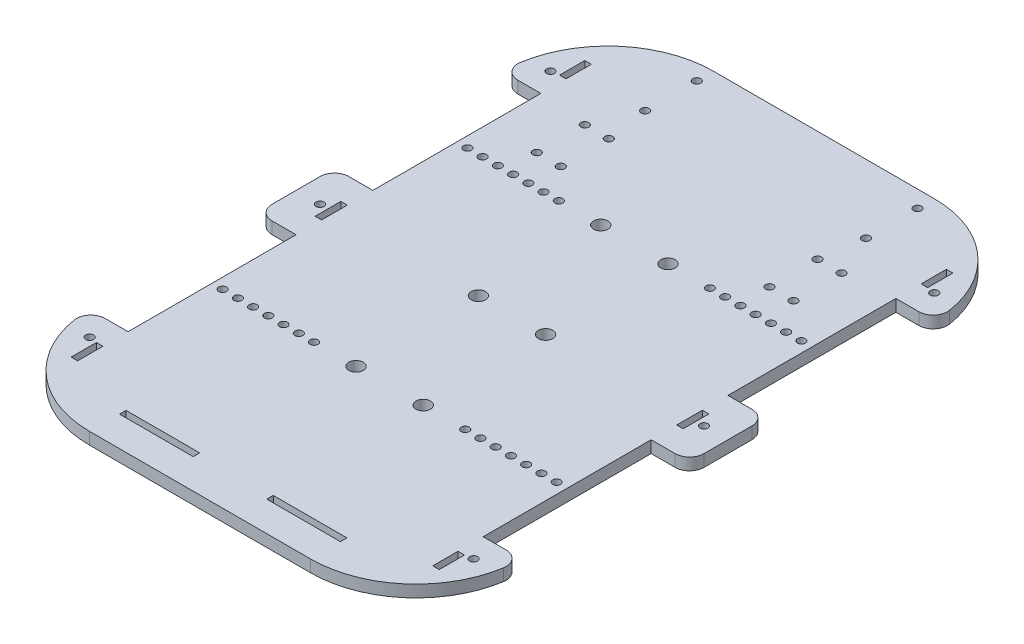
SolidWorks part; units mm, degrees
ref_plane "Ön Düzlem" through (0, 0, 0) normal (0, 0, 1) x (1, 0, 0)
ref_plane "Üst Düzlem" through (0, 0, 0) normal (0, 1, 0) x (1, 0, 0)
ref_plane "Sağ Düzlem" through (0, 0, 0) normal (1, 0, 0) x (0, 0, -1)
sketch "Sketch2" plane through (0, 0, 0) normal (0, 1, 0) x (1, 0, 0)
  line L0 (-74, -86) -> (-74, -51) construction
  line L1 (46, -130) -> (-46, -130)
  line L2 (90, -10) -> (90, 10)
  line L3 (46, 130) -> (-46, 130)
  line L4 (-90, -10) -> (-90, 10)
  line L5 (90, -130) -> (-90, 130) construction
  line L6 (90, 130) -> (-90, -130) construction
  line L7 (-83.5233, 86) -> (-74, 86)
  line L9 (-84, 16) -> (-74, 16)
  line L10 (-74, 86) -> (-74, 16)
  line L11 (-83.5233, -86) -> (-74, -86)
  line L13 (-84, -16) -> (-74, -16)
  line L14 (-74, -86) -> (-74, -16)
  line L15 (83.5233, 86) -> (74, 86)
  line L17 (84, 16) -> (74, 16)
  line L18 (74, 86) -> (74, 16)
  line L19 (83.5233, -86) -> (74, -86)
  line L21 (84, -16) -> (74, -16)
  line L22 (74, -86) -> (74, -16)
  line L23 (-74, 51) -> (74, 51) construction
  line L24 (-74, -51) -> (74, -51) construction
  line L26 (-74, 96.51) -> (-76.7, 96.51)
  line L27 (-76.7, 96.51) -> (-76.7, 107.02)
  line L28 (-74, 107.02) -> (-76.7, 107.02)
  line L29 (-74, 96.51) -> (-74, 107.02)
  line L30 (74, 96.51) -> (74, 107.02)
  line L31 (74, 107.02) -> (76.7, 107.02)
  line L32 (76.7, 96.51) -> (76.7, 107.02)
  line L33 (74, 96.51) -> (76.7, 96.51)
  line L34 (74, -107.02) -> (76.7, -107.02)
  line L35 (76.7, -96.51) -> (76.7, -107.02)
  line L36 (74, -96.51) -> (74, -107.02)
  line L37 (74, -96.51) -> (76.7, -96.51)
  line L38 (-74, -96.51) -> (-74, -107.02)
  line L39 (-74, -107.02) -> (-76.7, -107.02)
  line L40 (-76.7, -96.51) -> (-76.7, -107.02)
  line L41 (-74, -96.51) -> (-76.7, -96.51)
  line L42 (-74, 5.3333) -> (-74, -5.3333)
  line L43 (74, 5.3333) -> (74, -5.3333)
  line L44 (-74, 5.3333) -> (-76.7, 5.3333)
  line L45 (-76.7, 5.3333) -> (-76.7, -5.3333)
  line L46 (-76.7, -5.3333) -> (-74, -5.3333)
  line L47 (74, 5.3333) -> (76.7, 5.3333)
  line L48 (76.7, 5.3333) -> (76.7, -5.3333)
  line L49 (76.7, -5.3333) -> (74, -5.3333)
  line L52 (15.34, -117.53) -> (46.02, -117.53)
  line L54 (-15.34, -117.53) -> (-46.02, -117.53)
  line L56 (46.02, -117.53) -> (46.02, -114.83)
  line L57 (46.02, -114.83) -> (15.34, -114.83)
  line L59 (-15.34, -114.83) -> (-46.02, -114.83)
  line L60 (-46.02, -114.83) -> (-46.02, -117.53)
  line L62 (15.34, -117.53) -> (15.34, -114.83)
  line L63 (-15.34, -117.53) -> (-15.34, -114.83)
  arc A2 (-46, -130) -> (-89.4481, -92.9474) centre (-46, -86) cw
  arc A3 (-89.4481, 92.9474) -> (-46, 130) centre (-46, 86) cw
  arc A4 (89.4481, 92.9474) -> (46, 130) centre (46, 86) ccw
  arc A5 (89.4481, -92.9474) -> (46, -130) centre (46, -86) cw
  arc A6 (-84, 16) -> (-90, 10) centre (-84, 10) ccw
  arc A7 (-84, -16) -> (-90, -10) centre (-84, -10) cw
  arc A8 (90, 10) -> (84, 16) centre (84, 10) ccw
  arc A9 (90, -10) -> (84, -16) centre (84, -10) cw
  arc A10 (-89.4481, -92.9474) -> (-83.5233, -86) centre (-83.5233, -92) cw
  arc A11 (83.5233, -86) -> (89.4481, -92.9474) centre (83.5233, -92) cw
  arc A12 (-89.4481, 92.9474) -> (-83.5233, 86) centre (-83.5233, 92) ccw
  arc A13 (89.4481, 92.9474) -> (83.5233, 86) centre (83.5233, 92) cw
  point P0 (0, 0)
  point P34 (-90, -16)
  point P39 (90, -16)
  point P46 (-90, 86)
  point P49 (90, 86)
  dimension "D3" = 44
  dimension "D4" = 44
  dimension "D5" = 44
  dimension "D6" = 44
  dimension "D15" = 6
  dimension "D16" = 6
  dimension "D17" = 6
  dimension "D18" = 6
  dimension "D19" = 6
  dimension "D20" = 6
  dimension "D21" = 6
  dimension "D22" = 6
  dimension "D1" = 260
  dimension "D2" = 180
  dimension "D7" = 16
  dimension "D8" = 70
  dimension "D9" = 16
  dimension "D10" = 70
  dimension "D11" = 70
  dimension "D12" = 16
  dimension "D13" = 16
  dimension "D14" = 70
extrude "Boss-Extrude4" add sketch "Sketch2" along normal blind 5
sketch "Sketch5" plane through (0, 5, 0) normal (0, 1, 0) x (1, 0, 0)
  line L0 (-53.5, 63.83) -> (-43.5, 63.83) construction
  line L1 (-43.5, 63.83) -> (-43.5, 83.83) construction
  line L2 (-43.5, 83.83) -> (-43.5808, 83.8151) construction
  line L3 (-43.5808, 83.8151) -> (-53.5, 83.83) construction
  line L4 (-74, 86) -> (-74, 16) construction
  line L5 (53.5, 83.83) -> (43.5, 83.83) construction
  line L6 (43.5, 83.83) -> (43.5, 63.83) construction
  line L7 (43.5, 63.83) -> (53.5, 63.83) construction
  line L8 (74, 16) -> (74, 86) construction
  line L9 (46, 130) -> (-46, 130) construction
  circle A0 centre (-69.6, -51) radius 1.65
  circle A1 centre (-63.25, -51) radius 1.65
  circle A2 centre (-56.9, -51) radius 1.65
  circle A3 centre (-50.55, -51) radius 1.65
  circle A4 centre (-44.2, -51) radius 1.65
  circle A5 centre (-37.85, -51) radius 1.65
  circle A6 centre (-31.5, -51) radius 1.65
  circle A7 centre (31.5, -51) radius 1.65
  circle A8 centre (37.85, -51) radius 1.65
  circle A9 centre (44.2, -51) radius 1.65
  circle A10 centre (50.55, -51) radius 1.65
  circle A11 centre (56.9, -51) radius 1.65
  circle A12 centre (63.25, -51) radius 1.65
  circle A13 centre (69.6, -51) radius 1.65
  circle A14 centre (69.6, 51) radius 1.65
  circle A15 centre (63.25, 51) radius 1.65
  circle A16 centre (56.9, 51) radius 1.65
  circle A17 centre (50.55, 51) radius 1.65
  circle A18 centre (44.2, 51) radius 1.65
  circle A19 centre (37.85, 51) radius 1.65
  circle A20 centre (31.5, 51) radius 1.65
  circle A21 centre (-31.5, 51) radius 1.65
  circle A22 centre (-37.85, 51) radius 1.65
  circle A23 centre (-44.2, 51) radius 1.65
  circle A24 centre (-50.55, 51) radius 1.65
  circle A25 centre (-56.9, 51) radius 1.65
  circle A26 centre (-63.25, 51) radius 1.65
  circle A27 centre (-69.6, 51) radius 1.65
  circle A29 centre (-14, -51) radius 3
  circle A30 centre (14, -51) radius 3
  circle A31 centre (14, 51) radius 3
  circle A32 centre (-14, 51) radius 3
  circle A33 centre (-14, 0) radius 3
  circle A34 centre (14, 0) radius 3
  circle A35 centre (-80, 96) radius 1.65
  circle A36 centre (-80, 0) radius 1.65
  circle A37 centre (80, 0) radius 1.65
  circle A38 centre (-80, -96) radius 1.65
  circle A39 centre (80, -96) radius 1.65
  circle A40 centre (80, 96) radius 1.65
  circle A45 centre (-53.5, 83.83) radius 1.65
  circle A46 centre (-53.5, 63.83) radius 1.65
  circle A47 centre (-43.5, 63.83) radius 1.65
  circle A48 centre (-43.5, 83.83) radius 1.65
  circle A49 centre (43.5, 63.83) radius 1.65
  circle A50 centre (53.5, 63.83) radius 1.65
  circle A51 centre (43.5, 83.83) radius 1.65
  circle A52 centre (53.5, 83.83) radius 1.65
  circle A53 centre (-46, 123) radius 1.65
  circle A54 centre (-46, 101.5) radius 1.65
  circle A55 centre (46, 101.5) radius 1.65
  circle A56 centre (46, 123) radius 1.65
  dimension "D1" = 20.5
  dimension "D2" = 20.5
  dimension "D3" = 46.17
  dimension "D4" = 66.17
  dimension "D5" = 66.17
extrude "Cut-Extrude1" cut sketch "Sketch5" against normal through all
